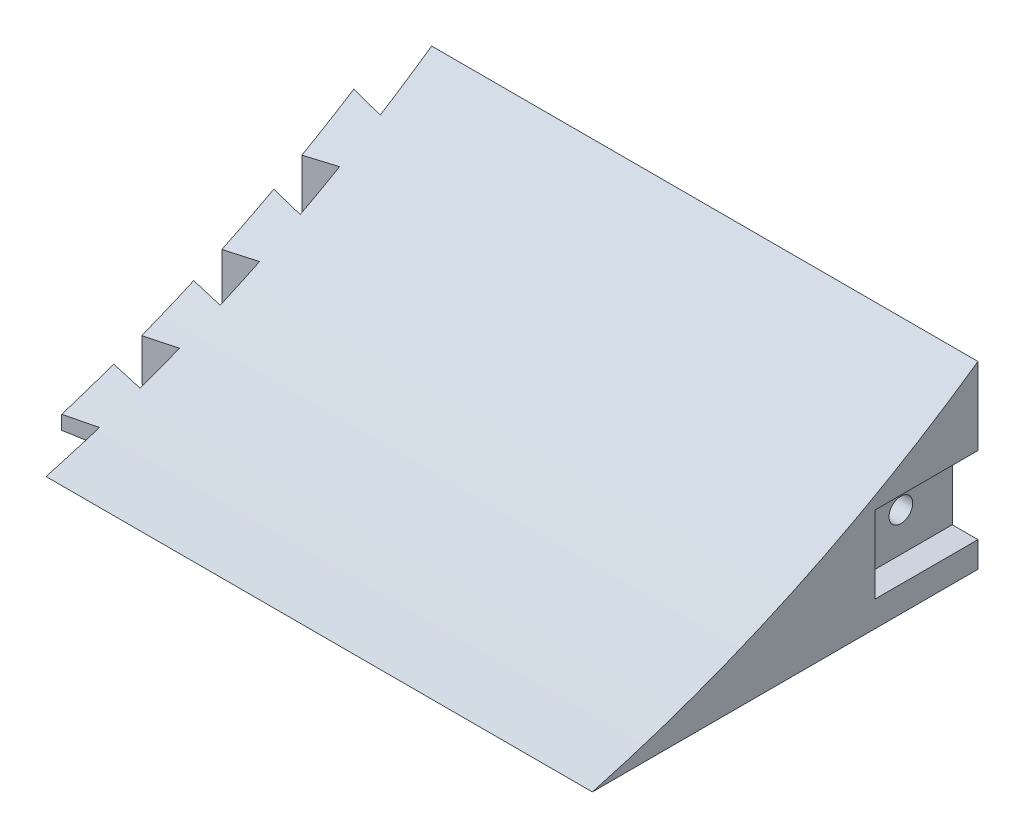
SolidWorks part; units mm, degrees
ref_plane "Front Plane" through (0, 0, 0) normal (0, 0, 1) x (1, 0, 0)
ref_plane "Top Plane" through (0, 0, 0) normal (0, 1, 0) x (1, 0, 0)
ref_plane "Right Plane" through (0, 0, 0) normal (1, 0, 0) x (0, 0, -1)
sketch "Sketch3" plane through (0, 0, 0) normal (1, 0, 0) x (0, 0, -1)
  line L0 (0, 0) -> (95.25, 0)
  line L1 (95.25, 0) -> (95.25, 44.45)
  arc A0 (0, 0) -> (95.25, 44.45) centre (-79.3399, 294.2927) ccw
  dimension "D3" = 304.8
  dimension "D1" = 44.45
  dimension "D2" = 95.25
extrude "Boss-Extrude1" add sketch "Sketch3" along normal blind 134.9375
sketch "Sketch4" plane through (134.9375, 0, 0) normal (1, 0, 0) x (0, 0, -1)
  line L6 (95.25, 0) -> (95.25, 44.45) construction
  line L7 (95.25, 25.4) -> (69.85, 25.4)
  line L8 (95.25, 25.4) -> (95.25, 6.35)
  line L9 (95.25, 6.35) -> (69.85, 6.35)
  line L10 (69.85, 25.4) -> (69.85, 6.35)
  line L11 (0, 0) -> (95.25, 0) construction
  dimension "D1" = 6.35
  dimension "D2" = 25.4
  dimension "D3" = 19.05
extrude "Cut-Extrude1" cut sketch "Sketch4" against normal blind 6.35
sketch "Sketch6" plane through (128.5875, 0, 0) normal (1, 0, 0) x (0, 0, -1)
  line L1 (69.85, 25.4) -> (69.85, 6.35) construction
  line L2 (69.85, 6.35) -> (95.25, 6.35) construction
  circle A0 centre (82.55, 15.875) radius 2.921
  dimension "D1" = 5.842
  dimension "D2" = 12.7
  dimension "D3" = 9.525
extrude "Cut-Extrude3" cut sketch "Sketch6" against normal blind 25.4
sketch "Sketch7" plane through (0, 0, 0) normal (0, -1, 0) x (1, 0, 0)
  line L0 (0, -82.55) -> (-7.9228, -83.947)
  line L1 (0, 0) -> (0, -95.25) construction
  line L2 (-7.9228, -83.947) -> (-7.9228, -71.12)
  line L3 (-7.9228, -71.12) -> (0, -72.517)
  line L4 (0, -82.55) -> (0, -72.517)
  line L5 (0, -62.7803) -> (-7.9228, -64.1773)
  line L6 (0, -62.7803) -> (0, -52.7473)
  line L7 (-7.9228, -51.3503) -> (0, -52.7473)
  line L8 (-7.9228, -64.1773) -> (-7.9228, -51.3503)
  line L9 (0, -43.0107) -> (-7.9228, -44.4077)
  line L10 (0, -43.0107) -> (0, -32.9777)
  line L11 (-7.9228, -31.5807) -> (0, -32.9777)
  line L12 (-7.9228, -44.4077) -> (-7.9228, -31.5807)
  line L13 (0, -23.241) -> (-7.9228, -24.638)
  line L14 (0, -23.241) -> (0, -13.208)
  line L15 (-7.9228, -11.811) -> (0, -13.208)
  line L16 (-7.9228, -24.638) -> (-7.9228, -11.811)
  dimension "D1" = 12.827
  dimension "D2" = 80
  dimension "D3" = 80
  dimension "D4" = 4
  dimension "D5" = 10.033
  dimension "D6" = 12.7
  dimension "D7" = 13.208
extrude "Boss-Extrude2" add sketch "Sketch7" against normal blind 38.1
sketch "Sketch8" plane through (134.9375, 0, 0) normal (1, 0, 0) x (0, 0, -1)
  line L1 (95.25, 44.45) -> (0, 44.45)
  line L2 (0, 44.45) -> (0, 0)
  arc A0 (0, 0) -> (95.25, 44.45) centre (-79.3399, 294.2927) ccw
  arc A1 (0, 0) -> (95.25, 44.45) centre (-79.3399, 294.2927) ccw construction
extrude "Cut-Extrude4" cut sketch "Sketch8" against normal through all
